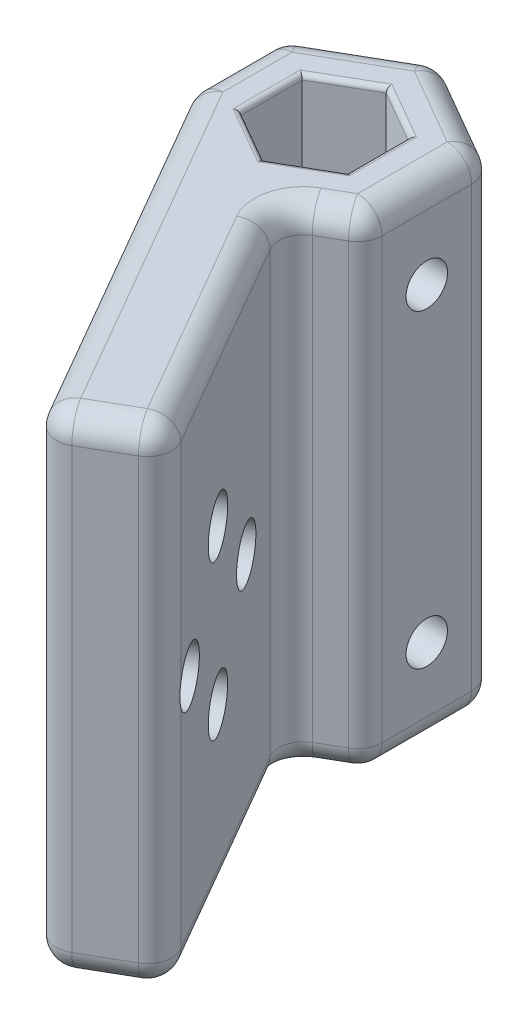
SolidWorks part; units mm, degrees
material "PET"
ref_plane "Front Plane" through (0, 0, 0) normal (0, 0, 1) x (1, 0, 0)
ref_plane "Top Plane" through (0, 0, 0) normal (0, 1, 0) x (1, 0, 0)
ref_plane "Right Plane" through (0, 0, 0) normal (1, 0, 0) x (0, 0, -1)
sketch "Sketch1" plane through (0, 0, 0) normal (0, 1, 0) x (1, 0, 0)
  line L0 (-4.775, -17.2483) -> (13.225, -48.4253)
  line L1 (6.55, -3.7816) -> (6.55, 3.7816)
  line L2 (6.55, 3.7816) -> (0, 7.5633)
  line L3 (0, 7.5633) -> (-6.55, 3.7816)
  line L4 (-6.55, 3.7816) -> (-6.55, -3.7816)
  line L5 (-6.55, -3.7816) -> (0, -7.5633)
  line L6 (0, -7.5633) -> (6.55, -3.7816)
  line L7 (3, -12.7594) -> (12.55, -7.2457) construction
  line L8 (12.55, -7.2457) -> (12.55, 7.2457)
  line L9 (12.55, 7.2457) -> (0, 14.4915)
  line L10 (0, 7.5633) -> (0, -7.5633) construction
  line L11 (0, 14.4915) -> (-12.55, 7.2457)
  line L12 (-12.55, 7.2457) -> (-12.55, -3.7816)
  line L13 (-12.55, -3.7816) -> (-4.775, -17.2483)
  line L14 (-4.775, -17.2483) -> (3, -12.7594) construction
  line L15 (5.6173, -11.2483) -> (23.6173, -42.4253)
  line L16 (13.225, -48.4253) -> (23.6173, -42.4253)
  line L17 (5.6173, -11.2483) -> (12.55, -7.2457)
  circle A0 centre (0, 0) radius 6.55 construction
  dimension "D1" = 13.1
  dimension "D2" = 30
  dimension "D3" = 36
  dimension "D5" = 12
  dimension "D4" = 6
extrude "Boss-Extrude1" add sketch "Sketch1" along normal mid plane 60
hole_wizard "CBORE for M3 SHCS1" positions "Sketch3" profile "Sketch4" counterbore size "M3" standard "ANSI Metric" end condition through all
sketch "Sketch3" plane through (-0.6577, 0, 0.3797) normal (0.866, 0, -0.5) x (-0.5, 0, -0.866)
  line L0 (-33.05, 9.5) -> (-33.05, -9.5) construction
  line L2 (-23.55, 0) -> (-42.55, 0) construction
  line L4 (-48.55, 30) -> (-48.55, -30) construction
  point P0 (-33.05, 9.5)
  point P2 (-42.55, 0)
  point P4 (-23.55, 0)
  point P6 (-33.05, -9.5)
  point P19 (-33.05, 0)
  point P20 (-33.05, 0)
  point P21 (-32.0423, -9.5)
  dimension "D1" = 19
  dimension "D2" = 6
sketch "Sketch4" plane through (15.8673, 9.5, 29.0019) normal (0, 1, 0) x (-0.5, 0, -0.866)
  line L0 (0, 0) -> (0, 34.3218)
  line L1 (0, 34.3218) -> (1.7, 34.3218)
  line L3 (1.7, 34.3218) -> (1.7, 3)
  line L4 (1.7, 3) -> (3.25, 3)
  line L5 (3.25, 3) -> (3.25, 0)
  line L7 (3.25, 0) -> (0, 0)
  line L11 (0, -6.35) -> (0, 107.95) construction
  dimension "Thru Hole Dia." = 3.4
  dimension "Thru Hole Depth" = 34.3218
  dimension "C'Bore Dia." = 6.5
  dimension "C'Bore Depth" = 3
hole_wizard "#10 Clearance Hole1" positions "Sketch5" profile "Sketch6" hole size "#10" standard "ANSI Inch" end condition through all
sketch "Sketch5" plane through (12.55, 0, 0) normal (1, 0, 0) x (0, 0, -1)
  line L0 (7.2457, 0) -> (-7.2457, 0) construction
  line L1 (7.2457, 30) -> (7.2457, -30) construction
  line L2 (-7.2457, 30) -> (-7.2457, -30) construction
  point P0 (0, -19.05)
  point P2 (0, 19.05)
  point P14 (0, 0)
  dimension "D1" = 38.1
sketch "Sketch6" plane through (12.55, -19.05, 0) normal (0, 1, 0) x (0, 0, -1)
  line L0 (0, 0) -> (0, 25.1)
  line L1 (0, 25.1) -> (2.5527, 25.1)
  line L2 (2.5527, 25.1) -> (2.5527, 0)
  line L5 (2.5527, 0) -> (0, 0)
  line L11 (0, -6.35) -> (0, 107.95) construction
  dimension "Thru Hole Dia." = 5.1054
  dimension "Thru Hole Depth" = 25.1
fillet "Fillet1" radius 3 24 edges at (9.0837, -30, 9.247) (9.0837, 30, 9.247) (12.55, 0, -7.2457) (6.275, 30, -10.8686) (0, 0, -14.4915) (6.275, -30, -10.8686) (-6.275, -30, -10.8686) (-12.55, -30, -1.7321) (0.3375, -30, 26.1034) (12.55, -30, 0) (12.55, 30, 0) (-6.275, 30, -10.8686) (-12.55, 30, -1.7321) (0.3375, 30, 26.1034) (18.4212, 30, 45.4253) (13.225, 0, 48.4253) (18.4212, -30, 45.4253) (14.6173, -30, 26.8368) (14.6173, 30, 26.8368) (23.6173, 0, 42.4253) (-12.55, 0, 3.7816) (-12.55, 0, -7.2457) (12.55, 0, 7.2457) (5.6173, 0, 11.2483)
fillet "Fillet2" radius 0.6 16 edges at (6.55, 30, 0) (3.275, 30, 5.6725) (3.275, 30, -5.6725) (-3.275, 30, -5.6725) (-6.55, 30, 0) (-3.275, 30, 5.6725) (-3.275, -30, -5.6725) (3.275, -30, -5.6725) (6.55, -30, 0) (3.275, -30, 5.6725) (-3.275, -30, 5.6725) (-6.55, -30, 0) (12.4192, 9.5, 29.0296) (17.1692, 0, 37.2569) (7.6692, 0, 20.8024) (12.4192, -9.5, 29.0296)
